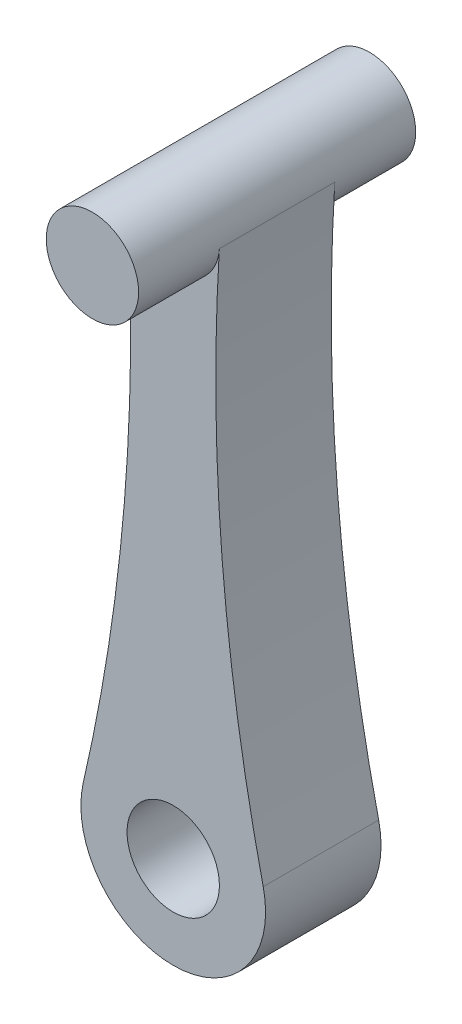
SolidWorks part; units mm, degrees
ref_plane "Front Plane" through (0, 0, 0) normal (0, 0, 1) x (1, 0, 0)
ref_plane "Top Plane" through (0, 0, 0) normal (0, 1, 0) x (1, 0, 0)
ref_plane "Right Plane" through (0, 0, 0) normal (1, 0, 0) x (0, 0, -1)
sketch "Sketch1" plane through (0, 0, 0) normal (0, 0, 1) x (1, 0, 0)
  line L0 (0, 60) -> (0, -60) construction
  circle A0 centre (0, -60) radius 10
  arc A1 (9.9808, 59.3801) -> (-9.9808, 59.3801) centre (0, 60) ccw
  arc A2 (-19.4863, -55.496) -> (19.4863, -55.496) centre (0, -60) ccw
  arc A3 (-9.9808, 59.3801) -> (-19.4863, -55.496) centre (-409.2114, 34.5833) cw
  arc A4 (9.9808, 59.3801) -> (19.4863, -55.496) centre (409.2114, 34.5833) ccw
  circle A5 centre (0, -60) radius 20 construction
  dimension "D1" = 20
  dimension "D4" = 400
  dimension "D2" = 120
  dimension "D3" = 10
extrude "Boss-Extrude1" add sketch "Sketch1" along normal blind 12.5 and the other way blind 12.5
sketch "Sketch2" plane through (0, 0, 12.5) normal (0, 0, 1) x (1, 0, 0)
  circle A0 centre (0, 60) radius 10
  arc A1 (9.9808, 59.3801) -> (-9.9808, 59.3801) centre (0, 60) ccw construction
extrude "Boss-Extrude2" add sketch "Sketch2" along normal blind 17.5
mirror "Mirror1" about plane through (0, 0, 0) normal (0, 0, 1) of "Boss-Extrude2"
